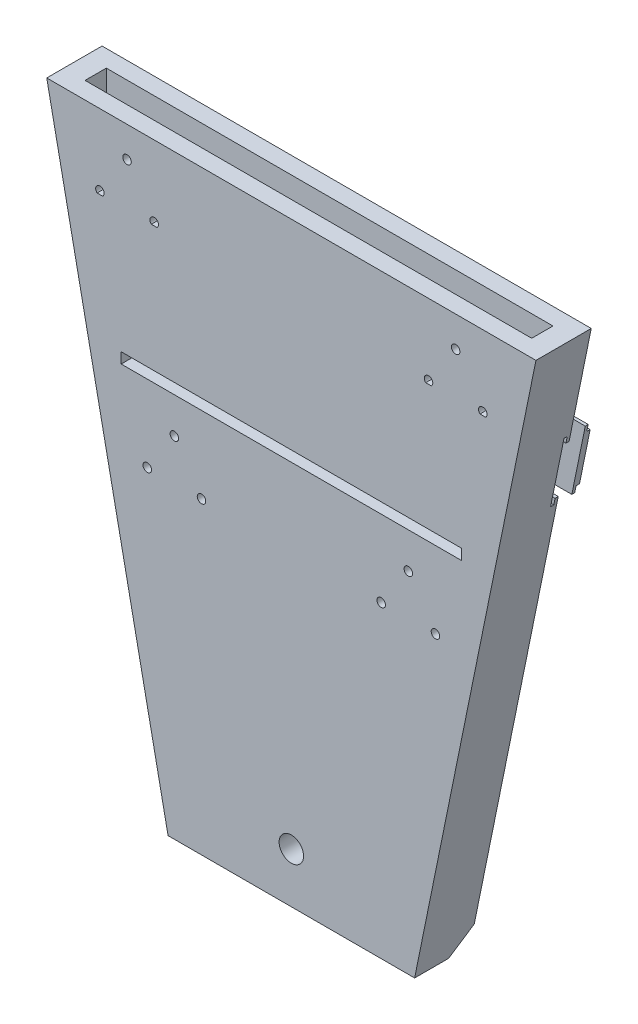
SolidWorks part; units mm, degrees
ref_plane "前视基准面" through (0, 0, 0) normal (0, 0, 1) x (1, 0, 0)
ref_plane "上视基准面" through (0, 0, 0) normal (0, 1, 0) x (1, 0, 0)
ref_plane "右视基准面" through (0, 0, 0) normal (1, 0, 0) x (0, 0, -1)
other "Configuration Table"
sketch "草图1" plane through (0, 0, 0) normal (0, 0, 1) x (1, 0, 0)
  line L0 (-60, 0) -> (60, 0)
  line L1 (0, 77.3448) -> (0, -71.5734) construction
  line L2 (-115, 270) -> (115, 270)
  line L3 (-115, 270) -> (-60, 0)
  line L4 (115, 270) -> (60, 0)
  point P3 (0, 0)
  point P8 (0, 270)
  dimension "D1" = 120
  dimension "D2" = 230
  dimension "D3" = 270
extrude "凸台-拉伸1" add sketch "草图1" along normal blind 8
sketch "草图2" plane through (0, 0, 8) normal (0, 0, 1) x (1, 0, 0)
  line L0 (-60, 0) -> (60, 0) construction
  line L1 (0, -1000) -> (0, 0.3) construction
  line L2 (0, 26.71) -> (0, 57.7278) construction
  line L3 (0.005, 0.31) -> (0, 0.3)
  line L4 (0, 26.71) -> (12.1089, 26.71)
  line L6 (0, 0.3) -> (17.4887, 0.3)
  line L7 (12.1089, 26.71) -> (17.4887, 0.3)
  line L8 (-115, 270) -> (-60, 0) construction
  arc A0 (0, 26.71) -> (0.005, 0.31) centre (0, 13.51) ccw
  dimension "D1" = 26.4
  dimension "D2" = 13.51
  dimension "D3" = 14.5
  dimension "D5" = 13.21
extrude "切除-拉伸1" cut sketch "草图2" against normal blind 8.6
sketch "草图3" plane through (0, 0, 8) normal (0, 0, 1) x (1, 0, 0)
  line L0 (-94.3261, 168.51) -> (94.3261, 168.51)
  line L1 (-115, 270) -> (-60, 0) construction
  line L2 (60, 0) -> (115, 270) construction
  line L4 (-96.3631, 178.51) -> (96.3631, 178.51)
  line L5 (-107.8704, 235) -> (107.8704, 235)
  point P0 (-115, 270)
  point P14 (0, 178.51)
  point P15 (0, 13.51)
  dimension "D1" = 155
  dimension "D2" = 10
  dimension "D3" = 35
sketch "草图5" plane through (0, 0, 0) normal (0, 0, -1) x (-1, 0, 0)
  line L4 (60, 0) -> (115, 270)
  line L5 (115, 270) -> (-115, 270)
  line L6 (-115, 270) -> (-60, 0)
  line L7 (-60, 0) -> (60, 0)
  line L8 (60, 0) -> (115, 270)
  line L9 (115, 270) -> (-115, 270)
  line L10 (-115, 270) -> (-60, 0)
  line L11 (-60, 0) -> (60, 0)
  dimension "D1" = 0
extrude "凸台-拉伸2" add sketch "草图5" along normal blind 8
sketch "草图6" plane through (0, 0, 8) normal (0, 0, 1) x (1, 0, 0)
  line L4 (-115, 270) -> (-60, 0)
  line L5 (-60, 0) -> (60, 0)
  line L6 (60, 0) -> (115, 270)
  line L7 (115, 270) -> (-115, 270)
  line L8 (-115, 270) -> (-60, 0)
  line L9 (-60, 0) -> (60, 0)
  line L10 (60, 0) -> (115, 270)
  line L11 (115, 270) -> (-115, 270)
  point P2 (0, 13.51)
  dimension "D1" = 0
extrude "凸台-拉伸3" add sketch "草图6" along normal blind 10
sketch "草图7" plane through (0, 0, 18) normal (0, 0, 1) x (1, 0, 0)
  circle A0 centre (0, 13.51) radius 5.75
  dimension "D1" = 11.5
extrude "切除-拉伸2" cut sketch "草图7" against normal blind 22
ref_plane "基准面1" through (0, 0, 18) normal (0, 0, 1) x (1, 0, 0)
sketch "草图9" plane through (0, 0, 18) normal (0, 0, 1) x (1, 0, 0)
  line L0 (-60, 0) -> (60, 0)
  line L1 (60, 0) -> (57.963, -10)
  line L2 (57.963, -10) -> (-57.963, -10)
  line L3 (-57.963, -10) -> (-60, 0)
  line L4 (60, 0) -> (115, 270) construction
  line L5 (-115, 270) -> (-60, 0) construction
  line L6 (60, 0) -> (115, 270)
  line L7 (-115, 270) -> (-60, 0)
  dimension "D1" = 10
extrude "凸台-拉伸5" add sketch "草图9" against normal blind 26 contours L3 L2 L1 L0 region at (0, -4.9712, 18)
ref_plane "基准面2" through (0, 0, -8) normal (0, 0, 1) x (1, 0, 0)
sketch "草图11" plane through (0, 0, -8) normal (0, 0, 1) x (1, 0, 0)
  line L0 (110.9179, 270) -> (53.8808, -10)
  line L1 (-110.9179, 270) -> (-53.8808, -10)
  line L2 (109.6932, 270) -> (52.6562, -10)
  line L3 (-109.6932, 270) -> (-52.6562, -10)
  line L4 (115, 270) -> (-115, 270)
  line L5 (-115, 270) -> (-57.963, -10)
  line L6 (-57.963, -10) -> (57.963, -10)
  line L7 (57.963, -10) -> (115, 270)
  line L8 (115, 270) -> (-115, 270)
  line L9 (-115, 270) -> (-57.963, -10)
  line L10 (-57.963, -10) -> (57.963, -10)
  line L11 (57.963, -10) -> (115, 270)
  dimension "D2" = 4
  dimension "D3" = 4
  dimension "D4" = 1.2
  dimension "D5" = 1.2
  dimension "D1" = 0
sketch "草图12" plane through (0, 0, -8) normal (0, 0, 1) x (1, 0, 0)
  line L0 (-115, 270) -> (-60, 0) construction
  line L1 (60, 0) -> (115, 270) construction
  line L2 (-115, 270) -> (-60, 0)
  line L3 (60, 0) -> (115, 270)
  line L4 (60, 0) -> (-60, 0)
  line L5 (57.963, -10) -> (60, 0)
  line L6 (-57.963, -10) -> (57.963, -10)
  line L7 (-60, 0) -> (-57.963, -10)
  line L8 (60, 0) -> (-60, 0)
  line L9 (57.963, -10) -> (60, 0)
  line L10 (-57.963, -10) -> (57.963, -10)
  line L11 (-60, 0) -> (-57.963, -10)
  line L12 (-109.6932, 270) -> (-52.6562, -10) construction
  line L13 (109.6932, 270) -> (52.6562, -10) construction
  line L14 (-110.9179, 270) -> (-53.8808, -10) construction
  line L15 (110.9179, 270) -> (53.8808, -10) construction
  line L16 (115, 270) -> (-115, 270)
  line L17 (-115, 270) -> (-57.963, -10)
  line L18 (-57.963, -10) -> (57.963, -10)
  line L19 (57.963, -10) -> (115, 270)
  line L20 (115, 270) -> (-115, 270)
  line L21 (-115, 270) -> (-57.963, -10)
  line L22 (-57.963, -10) -> (57.963, -10)
  line L23 (57.963, -10) -> (115, 270)
  line L24 (-109.6932, 270) -> (-52.6562, -10)
  line L25 (109.6932, 270) -> (52.6562, -10)
  line L26 (-110.9179, 270) -> (-53.8808, -10)
  line L27 (110.9179, 270) -> (53.8808, -10)
  dimension "D1" = 0
  dimension "D2" = 0
extrude "切除-拉伸4" cut sketch "草图12" along normal blind 21 contours L25 L8 L24 L22 region at (0, -4.9684, -8)
chamfer "倒角6" distance 5 angle 45 1 edges at (0, 0, -8)
chamfer "倒角8" distance 10 angle 45 2 edges at (-55.3096, -10, -8) (55.3096, -10, -8)
sketch "草图13" plane through (0, 270, 0) normal (0, 1, 0) x (1, 0, 0)
  line L1 (-105, 0) -> (105, 0)
  line L2 (-105, 0) -> (-105, -10)
  line L3 (-105, -10) -> (105, -10)
  line L4 (105, 0) -> (105, -10)
  line L5 (-105, 0) -> (105, -10) construction
  line L6 (-105, -10) -> (105, 0) construction
  line L7 (115, -18) -> (-115, -18) construction
  line L9 (-115, -18) -> (-115, 8) construction
  point P4 (0, -5)
  dimension "D1" = 210
  dimension "D2" = 10
  dimension "D3" = 13
  dimension "D4" = 115
extrude "切除-拉伸5" cut sketch "草图13" against normal blind 15
sketch "草图14" plane through (0, 0, 18) normal (0, 0, 1) x (1, 0, 0)
  line L0 (-96.3631, 178.51) -> (96.3631, 178.51) construction
  line L1 (-96.3631, 178.51) -> (96.3631, 178.51)
  line L2 (-94.3261, 168.51) -> (94.3261, 168.51) construction
  line L3 (-107.8704, 235) -> (107.8704, 235) construction
  line L4 (115, 270) -> (-115, 270)
  line L5 (-115, 270) -> (-57.963, -10)
  line L6 (-57.963, -10) -> (57.963, -10)
  line L7 (57.963, -10) -> (115, 270)
  line L8 (115, 270) -> (-115, 270)
  line L9 (-115, 270) -> (-57.963, -10)
  line L10 (-57.963, -10) -> (57.963, -10)
  line L11 (57.963, -10) -> (115, 270)
  line L12 (-94.3261, 168.51) -> (94.3261, 168.51)
  line L13 (-107.8704, 235) -> (107.8704, 235)
  line L14 (0, 270) -> (0, -10) construction
  line L15 (-80, 176.01) -> (80, 176.01)
  line L16 (-80, 176.01) -> (-80, 171.01)
  line L17 (-80, 171.01) -> (80, 171.01)
  line L18 (80, 176.01) -> (80, 171.01)
  line L19 (-80, 176.01) -> (80, 171.01) construction
  line L20 (-80, 171.01) -> (80, 176.01) construction
  point P14 (0, 173.51)
  dimension "D2" = 160
  dimension "D3" = 5
  dimension "D4" = 5
  dimension "D1" = 0
extrude "切除-拉伸6" cut sketch "草图14" against normal blind 10 contours L18 L15 L16 L17 region at (0, 173.51, 18)
sketch "草图16" plane through (0, 0, 18) normal (0, 0, 1) x (1, 0, 0)
  line L0 (0, 270) -> (0, -27.9065) construction
  line L2 (115, 270) -> (-115, 270) construction
  line L3 (-107.8704, 235) -> (107.8704, 235) construction
  line L4 (-94.3261, 168.51) -> (94.3261, 168.51) construction
  line L5 (-96.3631, 178.51) -> (96.3631, 178.51) construction
  line L6 (115, 270) -> (-115, 270)
  line L7 (-107.8704, 235) -> (107.8704, 235)
  line L8 (-94.3261, 168.51) -> (94.3261, 168.51)
  line L9 (-96.3631, 178.51) -> (96.3631, 178.51)
  line L11 (-90.2182, 178.51) -> (90.2182, 178.51)
  line L12 (-90.2182, 178.51) -> (-90.2182, 168.51)
  line L13 (-90.2182, 168.51) -> (90.2182, 168.51)
  line L14 (90.2182, 178.51) -> (90.2182, 168.51)
  line L15 (-90.2182, 178.51) -> (90.2182, 168.51) construction
  line L16 (-90.2182, 168.51) -> (90.2182, 178.51) construction
  circle A0 centre (-77.25, 255.6426) radius 2
  circle A1 centre (-90, 236.5) radius 2
  circle A2 centre (-64.5, 236.5) radius 2
  circle A3 centre (64.5, 236.5) radius 2
  circle A4 centre (90, 236.5) radius 2
  circle A5 centre (77.25, 255.6426) radius 2
  circle A6 centre (-55, 154.1526) radius 2
  circle A7 centre (-67.75, 135.01) radius 2
  circle A8 centre (-42.25, 135.01) radius 2
  circle A9 centre (42.25, 135.01) radius 2
  circle A10 centre (67.75, 135.01) radius 2
  circle A11 centre (55, 154.1526) radius 2
  point P15 (0, 173.51)
  dimension "D6" = 4
  dimension "D7" = 4
  dimension "D8" = 4
  dimension "D15" = 4
  dimension "D16" = 4
  dimension "D17" = 4
  dimension "D1" = 33.5
  dimension "D2" = 33.5
  dimension "D3" = 25.5
  dimension "D4" = 23
  dimension "D5" = 23
  dimension "D9" = 90
  dimension "D10" = 23
  dimension "D11" = 23
  dimension "D12" = 25.5
  dimension "D13" = 33.5
  dimension "D14" = 33.5
  dimension "D18" = 55
extrude "切除-拉伸7" cut sketch "草图16" against normal blind 10 contours A0 | A1 | A2 | A5 | A3 | A4 | A6 | A8 | A11 | A9 | A10 | A7 region at (-90, 236.6324, 18) region at (90, 236.6324, 18) region at (64.5, 236.6324, 18) region at (-64.5, 236.6324, 18) region at (-77.25, 255.6426, 18) region at (77.25, 255.6426, 18) region at (-55, 154.1526, 18) region at (-42.25, 135.01, 18) region at (42.25, 135.01, 18) region at (67.75, 135.01, 18) region at (55, 154.1526, 18)
sketch "草图17" plane through (0, 0, 18) normal (0, 0, 1) x (1, 0, 0)
  point P0 (-60.2489, 215.8027)
  point P1 (0, 0)
  point P2 (-96.3631, 178.51)
sketch "草图18" plane through (0, 0, 0) normal (0, -1, 0) x (1, 0, 0)
  line L4 (-54.6932, 13) -> (-54.6932, -3)
  line L5 (-54.6932, -3) -> (54.6932, -3)
  line L6 (54.6932, -3) -> (54.6932, 13)
  line L7 (54.6932, 13) -> (-54.6932, 13)
  line L8 (-54.6932, 13) -> (-54.6932, -3)
  line L10 (54.6932, -3) -> (54.6932, 13)
  line L11 (54.6932, 13) -> (-54.6932, 13)
  line L13 (-54.6932, -3) -> (54.6932, -3)
  dimension "D1" = 0
extrude "凸台-拉伸7" add sketch "草图18" along normal blind 2
chamfer "倒角10" distance 2 angle 45 1 edges at (0, -2, -3)
sketch "草图32" plane through (0, 0, -8) normal (0, 0, -1) x (-1, 0, 0)
  line L0 (-96.3631, 178.51) -> (-96.3631, 232.5516) construction
  line L2 (-96.3631, 218.8405) -> (3.6369, 218.8405)
  line L3 (-96.3631, 218.8405) -> (-96.3631, 193.8405)
  line L4 (-96.3631, 193.8405) -> (3.6369, 193.8405)
  line L5 (3.6369, 218.8405) -> (3.6369, 193.8405)
  line L6 (-96.3631, 218.8405) -> (3.6369, 193.8405) construction
  line L7 (-96.3631, 193.8405) -> (3.6369, 218.8405) construction
  line L8 (55.7117, 5) -> (54.6932, 0)
  line L9 (54.6932, 0) -> (60, 0)
  line L10 (60, 0) -> (115, 270)
  line L11 (115, 270) -> (-115, 270)
  line L12 (-115, 270) -> (-60, 0)
  line L13 (-60, 0) -> (-54.6932, 0)
  line L14 (-54.6932, 0) -> (-55.7117, 5)
  line L15 (-55.7117, 5) -> (55.7117, 5)
  line L16 (55.7117, 5) -> (54.6932, 0)
  line L17 (54.6932, 0) -> (60, 0)
  line L18 (60, 0) -> (115, 270)
  line L19 (115, 270) -> (-115, 270)
  line L20 (-115, 270) -> (-60, 0)
  line L21 (-60, 0) -> (-54.6932, 0)
  line L22 (-54.6932, 0) -> (-55.7117, 5)
  line L23 (-55.7117, 5) -> (55.7117, 5)
  point P14 (-46.3631, 206.3405)
  dimension "D2" = 100
  dimension "D3" = 25
  dimension "D1" = 0
extrude "切除-拉伸16" cut sketch "草图32" against normal blind 3 contours L5 L2 L3 L4 region at (46.3631, 206.3405, -8)
sketch "草图33" plane through (-3.6369, 0, 0) normal (1, 0, 0) x (0, 0, -1)
  line L4 (8, 193.8405) -> (8, 218.8405)
  line L5 (8, 218.8405) -> (5, 218.8405)
  line L6 (5, 218.8405) -> (5, 193.8405)
  line L7 (5, 193.8405) -> (8, 193.8405)
  line L8 (8, 193.8405) -> (8, 218.8405)
  line L9 (8, 218.8405) -> (5, 218.8405)
  line L10 (5, 218.8405) -> (5, 193.8405)
  line L11 (5, 193.8405) -> (8, 193.8405)
  dimension "D1" = 0
extrude "切除-拉伸17" cut sketch "草图33" along normal blind 1003
sketch "草图34" plane through (-3.6369, 0, 0) normal (1, 0, 0) x (0, 0, -1)
  line L0 (5, 193.8405) -> (8, 193.8405) construction
  line L1 (5, 218.8405) -> (6.5, 218.8405)
  line L2 (5, 218.8405) -> (5, 193.8405)
  line L3 (5, 193.8405) -> (6.5, 193.8405)
  line L4 (6.5, 218.8405) -> (6.5, 193.8405)
  line L5 (5, 218.8405) -> (6.5, 193.8405) construction
  line L6 (5, 193.8405) -> (6.5, 218.8405) construction
  point P4 (5.75, 206.3405)
extrude "切除-拉伸19" cut sketch "草图34" against normal blind 3
sketch "草图36" plane through (0, 218.8405, 0) normal (0, -1, 0) x (1, 0, 0)
  line L1 (-6.6369, -5) -> (104.5786, -5)
  line L2 (-6.6369, -5) -> (-6.6369, -6.5)
  line L3 (-6.6369, -6.5) -> (104.5786, -6.5)
  line L4 (104.5786, -5) -> (104.5786, -6.5)
  line L5 (-6.6369, -5) -> (104.5786, -6.5) construction
  line L6 (-3.6369, -8) -> (104.5786, -8)
  line L7 (104.5786, -8) -> (104.5786, -5)
  line L8 (104.5786, -5) -> (-6.6369, -5)
  line L9 (-6.6369, -5) -> (-6.6369, -6.5)
  line L10 (-6.6369, -6.5) -> (-3.6369, -6.5)
  line L11 (-3.6369, -6.5) -> (-3.6369, -8)
  line L12 (-3.6369, -8) -> (104.5786, -8) construction
  line L13 (104.5786, -8) -> (104.5786, -5) construction
  line L14 (104.5786, -5) -> (-6.6369, -5) construction
  line L15 (-6.6369, -5) -> (-6.6369, -6.5) construction
  line L16 (-6.6369, -6.5) -> (-3.6369, -6.5) construction
  line L17 (-3.6369, -6.5) -> (-3.6369, -8) construction
  line L18 (-6.6369, -6.5) -> (104.5786, -5) construction
  point P4 (48.9709, -5.75)
  dimension "D1" = 0
extrude "切除-拉伸20" cut sketch "草图36" against normal blind 3
sketch "草图37" plane through (0, 193.8405, 0) normal (0, 1, 0) x (1, 0, 0)
  line L1 (-6.6369, 5) -> (99.486, 5)
  line L2 (-6.6369, 5) -> (-6.6369, 6.5)
  line L3 (-6.6369, 6.5) -> (99.486, 6.5)
  line L4 (99.486, 5) -> (99.486, 6.5)
  line L5 (-6.6369, 5) -> (99.486, 6.5) construction
  line L6 (99.486, 8) -> (-3.6369, 8)
  line L7 (-3.6369, 8) -> (-3.6369, 6.5)
  line L8 (-3.6369, 6.5) -> (-6.6369, 6.5)
  line L9 (-6.6369, 6.5) -> (-6.6369, 5)
  line L10 (-6.6369, 5) -> (99.486, 5)
  line L11 (99.486, 5) -> (99.486, 8)
  line L12 (99.486, 8) -> (-3.6369, 8) construction
  line L13 (-3.6369, 8) -> (-3.6369, 6.5)
  line L14 (-3.6369, 6.5) -> (-6.6369, 6.5)
  line L15 (-6.6369, 6.5) -> (-6.6369, 5) construction
  line L16 (-6.6369, 5) -> (99.486, 5) construction
  line L17 (99.486, 5) -> (99.486, 8) construction
  line L18 (-6.6369, 6.5) -> (99.486, 5) construction
  point P4 (46.4246, 5.75)
  line M9 (-3.6369, 6.5) -> (-6.6369, 6.5)
  line M10 (-6.6369, 6.5) -> (-6.6369, 5)
  line M11 (-6.6369, 5) -> (99.486, 5)
  line M12 (99.486, 5) -> (99.486, 8)
  dimension "D1" = 0
extrude "切除-拉伸21" cut sketch "草图37" against normal blind 3 contours L3 M9 M10 M11 M12 region at (46.4246, 193.8405, -5.75)
sketch "草图38" plane through (-6.6369, 0, 0) normal (1, 0, 0) x (0, 0, -1)
  line L4 (5, 221.8405) -> (5, 190.8405)
  line L5 (5, 190.8405) -> (6.5, 190.8405)
  line L6 (6.5, 190.8405) -> (6.5, 221.8405)
  line L7 (6.5, 221.8405) -> (5, 221.8405)
  line L8 (5, 221.8405) -> (5, 190.8405)
  line L9 (5, 190.8405) -> (6.5, 190.8405)
  line L10 (6.5, 190.8405) -> (6.5, 221.8405)
  line L11 (6.5, 221.8405) -> (5, 221.8405)
  dimension "D1" = 0
extrude "切除-拉伸22" cut sketch "草图38" along normal blind 1003
ref_plane "基准面3" through (0, 0, -15) normal (0, 0, -1) x (-1, 0, 0)
sketch "草图39" plane through (0, 0, -15) normal (0, 0, -1) x (-1, 0, 0)
  line L4 (-105.1897, 221.8405) -> (-98.8749, 190.8405)
  line L5 (-98.8749, 190.8405) -> (6.6369, 190.8405)
  line L6 (6.6369, 190.8405) -> (6.6369, 221.8405)
  line L7 (6.6369, 221.8405) -> (-105.1897, 221.8405)
  line L8 (-105.1897, 221.8405) -> (-98.8749, 190.8405)
  line L9 (-98.8749, 190.8405) -> (6.6369, 190.8405)
  line L10 (6.6369, 190.8405) -> (6.6369, 221.8405)
  line L11 (6.6369, 221.8405) -> (-105.1897, 221.8405)
  dimension "D1" = 0
extrude "凸台-拉伸8" add sketch "草图39" along normal blind 1.35 separate body
sketch "草图41" plane through (0, 0, -16.35) normal (0, 0, -1) x (-1, 0, 0)
  line L4 (6.6369, 221.8405) -> (-105.1897, 221.8405)
  line L5 (-105.1897, 221.8405) -> (-98.8749, 190.8405)
  line L6 (-98.8749, 190.8405) -> (6.6369, 190.8405)
  line L7 (6.6369, 190.8405) -> (6.6369, 221.8405)
  line L8 (6.6369, 221.8405) -> (-105.1897, 221.8405) construction
  line L9 (-105.1897, 221.8405) -> (-98.8749, 190.8405) construction
  line L10 (-98.8749, 190.8405) -> (6.6369, 190.8405) construction
  line L11 (6.6369, 190.8405) -> (6.6369, 221.8405) construction
  line L12 (-101.2722, 218.6405) -> (-104.5379, 218.6405)
  line L13 (-96.261, 194.0405) -> (-99.5268, 194.0405)
  line L14 (-104.5379, 218.6405) -> (-99.5268, 194.0405)
  line L16 (3.4369, 218.6405) -> (-101.2722, 218.6405)
  line L17 (-101.2722, 218.6405) -> (-96.261, 194.0405)
  line L18 (-96.261, 194.0405) -> (3.4369, 194.0405)
  line L19 (3.4369, 194.0405) -> (3.4369, 218.6405)
  line L20 (3.4369, 218.6405) -> (-101.2722, 218.6405)
  line L22 (-96.261, 194.0405) -> (3.4369, 194.0405)
  line L23 (3.4369, 194.0405) -> (3.4369, 218.6405)
  dimension "D1" = 0
  dimension "D2" = 3.2
extrude "凸台-拉伸9" add sketch "草图41" along normal blind 1.6
sketch "草图42" plane through (0, 0, -17.95) normal (0, 0, -1) x (-1, 0, 0)
  line L0 (-99.5268, 206.3405) -> (3.4369, 206.3405) construction
  line L1 (3.4369, 218.6405) -> (-99.5268, 218.6405) construction
  line L2 (3.4369, 218.6405) -> (3.4369, 194.0405) construction
  line L3 (3.4369, 194.0405) -> (-99.5268, 194.0405) construction
  line L4 (-99.5268, 218.6405) -> (-99.5268, 194.0405) construction
  line L5 (3.4369, 218.6405) -> (-99.5268, 194.0405) construction
  line L6 (3.4369, 194.0405) -> (-99.5268, 218.6405) construction
  point P4 (-48.045, 206.3405)
